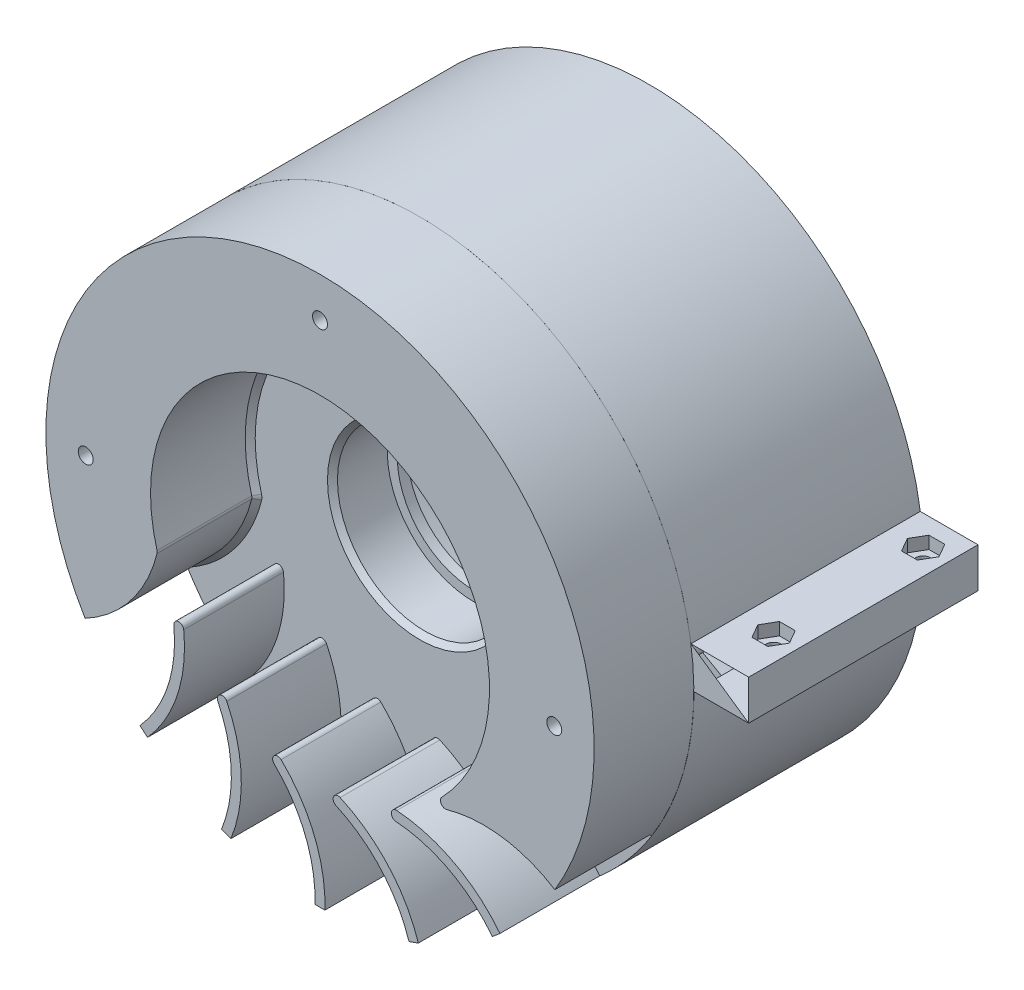
SolidWorks part; units mm, degrees
ref_plane "前视基准面" through (0, 0, 0) normal (0, 0, 1) x (1, 0, 0)
ref_plane "上视基准面" through (0, 0, 0) normal (0, 1, 0) x (1, 0, 0)
ref_plane "右视基准面" through (0, 0, 0) normal (1, 0, 0) x (0, 0, -1)
other "Configuration Table"
sketch "草图1" plane through (0, 0, 0) normal (1, 0, 0) x (0, 0, -1)
  line L0 (0, 0) -> (32.5576, 0) construction
  line L1 (0, 17.5) -> (46, 17.5)
  line L2 (0, 17.5) -> (0, 55)
  line L3 (0, 55) -> (46, 55)
  line L4 (46, 17.5) -> (46, 55)
  dimension "D1" = 17.5
  dimension "D2" = 55
  dimension "D3" = 46
sketch "草图2" plane through (0, 0, 0) normal (0, 0, 1) x (1, 0, 0)
  line L0 (-33.6531, -9.6161) -> (-22.355, -49.1554) construction
  line L3 (-52.8896, -16.3925) -> (-45.4407, -29.2943) construction
  line L4 (-45.7638, -26.4218) -> (-39.6155, -22.872) construction
  line L5 (0, 0) -> (0, -27.9556) construction
  line L6 (-33.6531, -9.6161) -> (-40.2555, -35.993) construction
  circle A0 centre (0, 0) radius 35 construction
  circle A1 centre (0, 0) radius 54 construction
  arc A4 (-33.6531, -9.6161) -> (-46.7654, -27) centre (-60.7125, -2.8429) cw construction
  arc A5 (-46.2654, -27.866) -> (-32.683, -9.859) centre (-60.7125, -2.8429) ccw
  arc A6 (-47.2654, -26.134) -> (-34.6231, -9.3733) centre (-60.7125, -2.8429) ccw
  arc A7 (-47.2654, -26.134) -> (-46.2654, -27.866) centre (-46.7654, -27) ccw construction
  arc A8 (-32.683, -9.859) -> (-34.6231, -9.3733) centre (-33.6531, -9.6161) ccw
  arc A9 (-47.2654, -26.134) -> (-48.1283, -26.6113) centre (-60.7125, -2.8429) cw
  arc A10 (-54.7677, -5.0001) -> (54.7677, -5.0001) centre (0, 0) ccw construction
  arc A11 (-46.2654, -27.866) -> (-47.1283, -28.3448) centre (-60.7125, -2.8429) cw
  arc A12 (-47.1283, -28.3448) -> (-48.1283, -26.6113) centre (0, 0) cw
  point P6 (-38.4429, -19.6404)
  dimension "D1" = 70
  dimension "D2" = 108
  dimension "D3" = 1
  dimension "D4" = 60
  dimension "D5" = 30
extrude "凸台-拉伸1" add sketch "草图2" along normal blind 20 contours A12 A11 A5 A8 A6 A9 region at (-39.1834, -19.2063, 0)
revolve "旋转1" add sketch "草图1" angle 360 about L0
pattern_circular "阵列(圆周)1" count 7 every 20 about axis through (0, 0, 0) along (0, 0, 1) of "凸台-拉伸1"
sketch "草图3" plane through (0, 0, 0) normal (0, 0, 1) x (1, 0, 0)
  arc A9 (-47.1283, -28.3448) -> (47.1103, -28.3747) centre (0, 0) cw
  arc A20 (-32.6916, -9.3414) -> (24.4357, -23.641) centre (0, 0) cw
  arc A22 (24.8796, -23.3748) -> (25.4291, -25.2979) centre (25.1544, -24.3363) ccw construction
  arc A23 (-47.1283, -28.3448) -> (-32.683, -9.859) centre (-60.7125, -2.8429) ccw construction
  arc A24 (-47.1283, -28.3448) -> (-32.683, -9.859) centre (-60.7125, -2.8429) ccw
  arc A25 (47.1103, -28.3747) -> (25.4291, -25.2979) centre (32.8182, -51.1571) ccw
  arc A26 (-32.683, -9.859) -> (-32.6916, -9.3414) centre (-33.6531, -9.6161) ccw
  arc A27 (24.4357, -23.641) -> (25.4291, -25.2979) centre (25.1544, -24.3363) ccw
  arc A28 (47.1103, -28.3747) -> (25.4291, -25.2979) centre (32.8182, -51.1571) ccw construction
extrude "凸台-拉伸2" add sketch "草图3" along normal up to surface (20 mm away) up to face at (-39.6333, -19.0479, 20)
sketch "草图4" plane through (0, 0, -46) normal (0, 0, -1) x (-1, 0, 0)
  line L0 (-50, 0) -> (-47, 0) construction
  line L1 (-45.25, 3.0311) -> (-49.6863, 5.5924)
  line L2 (-45.25, -3.0311) -> (-49.6863, -5.5924)
  line L3 (3.0311, 45.25) -> (5.5924, 49.6863)
  line L4 (-3.0311, 45.25) -> (-5.5924, 49.6863)
  line L5 (0, 50) -> (0, 47) construction
  line L6 (45.25, -3.0311) -> (49.6863, -5.5924)
  line L7 (45.25, 3.0311) -> (49.6863, 5.5924)
  line L8 (50, 0) -> (47, 0) construction
  line L9 (-3.0311, -45.25) -> (-5.5924, -49.6863)
  line L10 (3.0311, -45.25) -> (5.5924, -49.6863)
  line L11 (0, -50) -> (0, -47) construction
  line L12 (-49.9706, -1.7151) -> (-49.9706, 1.7151) construction
  line L13 (-49.9706, 1.7151) -> (-47, 0) construction
  circle A0 centre (0, 0) radius 50 construction
  circle A1 centre (0, 0) radius 55 construction
  arc A2 (-45.25, -3.0311) -> (-45.25, 3.0311) centre (-47, 0) ccw
  circle A3 centre (-47, 0) radius 1.5
  arc A4 (-49.6863, 5.5924) -> (-35.3553, 35.3553) centre (0, 0) cw
  arc A5 (-49.6863, -5.5924) -> (-31.1791, -39.0879) centre (0, 0) ccw
  arc A6 (-3.0311, 45.25) -> (3.0311, 45.25) centre (0, 47) ccw
  circle A7 centre (0, 47) radius 1.5
  arc A8 (5.5924, 49.6863) -> (35.3553, 35.3553) centre (0, 0) cw
  arc A9 (-5.5924, 49.6863) -> (-39.0879, 31.1791) centre (0, 0) ccw
  arc A10 (45.25, 3.0311) -> (45.25, -3.0311) centre (47, 0) ccw
  circle A11 centre (47, 0) radius 1.5
  arc A12 (49.6863, -5.5924) -> (35.3553, -35.3553) centre (0, 0) cw
  arc A13 (49.6863, 5.5924) -> (31.1791, 39.0879) centre (0, 0) ccw
  arc A14 (3.0311, -45.25) -> (-3.0311, -45.25) centre (0, -47) ccw
  circle A15 centre (0, -47) radius 1.5
  arc A16 (-5.5924, -49.6863) -> (-35.3553, -35.3553) centre (0, 0) cw
  arc A17 (5.5924, -49.6863) -> (39.0879, -31.1791) centre (0, 0) ccw
  point P44 (0, 0)
  circle M8 centre (0, 0) radius 17.5
  dimension "D1" = 5
  dimension "D2" = 3
  dimension "D3" = 2
  dimension "D6" = 45
  dimension "D4" = 30
  dimension "D5" = 30
  dimension "D7" = 45
  dimension "D10" = 60
  dimension "D11" = 47
  dimension "D8" = 4
extrude "切除-拉伸1" cut sketch "草图4" against normal offset from surface (35 mm away) 11 contours L10 A17 A12 L6 A10 L7 A13 A8 L3 A6 L4 A9 A4 L1 A2 L2 A5 A16 L9 A14 M8 | A7 | A11 | A15 | A3 region at (46.7655, 5.5288, -46) region at (47, 0, -46) region at (0, 47, -46) region at (-47, 0, -46) region at (0, -47, -46) up to face at (25.6408, -35.7236, 0)
sketch "草图5" plane through (0, 0, -11) normal (0, 0, -1) x (-1, 0, 0)
  circle A0 centre (-47, 0) radius 1.5 construction
  circle A1 centre (0, 47) radius 1.5
  circle A2 centre (0, 47) radius 1.5
  circle A3 centre (-47, 0) radius 1.5
  circle A6 centre (47, 0) radius 1.5 construction
  circle A7 centre (47, 0) radius 1.5
  dimension "D1" = 0
extrude "切除-拉伸2" cut sketch "草图5" against normal up to surface (31 mm away) up to face at (-0.2385, 1.394, 20)
sketch "草图7" plane through (0, 0, -11) normal (0, 0, -1) x (-1, 0, 0)
  circle A10 centre (0, 0) radius 19.5
  circle A11 centre (0, 0) radius 19.5
  circle A12 centre (0, 0) radius 15.5
  circle A13 centre (0, 0) radius 15.5
  dimension "D1" = 2
  dimension "D2" = 2
extrude "凸台-拉伸3" add sketch "草图7" along normal blind 2
chamfer "倒角2" distance 1 angle 45 1 edges at (17.5, 0, 0)
chamfer "倒角3" distance 1 angle 45 4 edges at (-37.9451, -20.6339, 0) (-32.6532, -9.5996, 0) (24.2967, -24.8506, 0) (8.2559, 32.9824, 0)
sketch "草图9" plane through (0, 0, 0) normal (0, 1, 0) x (1, 0, 0)
  line L0 (-55, 46) -> (-55, 0) construction
  line L11 (-55, 46) -> (-55, 0)
  line L12 (-55, 46) -> (-66, 46)
  line L13 (-66, 46) -> (-66, 0)
  line L14 (-66, 0) -> (-55, 0)
  line L15 (0, -36.3) -> (0, 36.3) construction
  line L16 (66, 46) -> (66, 0)
  line L17 (55, 46) -> (66, 46)
  line L18 (55, 46) -> (55, 0)
  line L19 (66, 0) -> (55, 0)
  dimension "D1" = 11
extrude "凸台-拉伸4" add sketch "草图9" along normal blind 8
sketch "草图12" plane through (-55, 0, 0) normal (1, 0, 0) x (0, 0, -1)
  line L4 (0, 0) -> (46, 0)
  line L5 (46, 0) -> (46, 8)
  line L6 (46, 8) -> (0, 8)
  line L7 (0, 8) -> (0, 0)
  line L8 (0, 0) -> (46, 0)
  line L9 (46, 0) -> (46, 8)
  line L10 (46, 8) -> (0, 8)
  line L11 (0, 8) -> (0, 0)
  dimension "D1" = 0
extrude "凸台-拉伸6" add sketch "草图12" along normal up to next
sketch "草图14" plane through (0, 0, 0) normal (0, -1, 0) x (1, 0, 0)
  line L0 (-61, -10) -> (-61, -40) construction
  line L1 (0, -36.3) -> (0, 36.3) construction
  line L4 (-66, -46) -> (-55, -46)
  line L5 (-55, -46) -> (-55, 0)
  line L6 (-55, 0) -> (-66, 0)
  line L7 (-66, 0) -> (-66, -46)
  line L8 (-66, -46) -> (-55, -46) construction
  line L10 (-55, 0) -> (-66, 0) construction
  line L11 (-66, 0) -> (-66, -46) construction
  line L13 (-55, -46) -> (-55, 0)
  circle A0 centre (-61, -10) radius 1.5
  circle A1 centre (-61, -40) radius 1.5
  circle A2 centre (61, -40) radius 1.5
  circle A3 centre (61, -10) radius 1.5
  dimension "D2" = 3
  dimension "D5" = 3
  dimension "D3" = 10
  dimension "D4" = 6
  dimension "D6" = 30
  dimension "D1" = 0
extrude "切除-拉伸3" cut sketch "草图14" against normal up to next contours A1 | A0 | A1 | A3 | A2 region at (-61, 0, -40)
sketch "草图15" plane through (55, 0, 0) normal (-1, 0, 0) x (0, 0, 1)
  line L4 (-46, 0) -> (0, 0)
  line L5 (0, 0) -> (0, 8)
  line L6 (0, 8) -> (-46, 8)
  line L7 (-46, 8) -> (-46, 0)
  line L8 (-46, 0) -> (0, 0)
  line L9 (0, 0) -> (0, 8)
  line L10 (0, 8) -> (-46, 8)
  line L11 (-46, 8) -> (-46, 0)
  dimension "D1" = 0
extrude "凸台-拉伸7" add sketch "草图15" along normal up to next
sketch "草图17" plane through (0, 0, 0) normal (0, -1, 0) x (1, 0, 0)
  line L0 (-61, -10) -> (-61, -40) construction
  line L1 (-57.8246, -40) -> (-59.4123, -37.25)
  line L2 (-59.4123, -37.25) -> (-62.5877, -37.25)
  line L3 (-62.5877, -37.25) -> (-64.1754, -40)
  line L4 (-66, -46) -> (-55, -46)
  line L5 (-55, -46) -> (-55, 0)
  line L6 (-55, 0) -> (-66, 0)
  line L7 (-66, 0) -> (-66, -46)
  line L8 (-66, -46) -> (-55, -46) construction
  line L9 (-55, -46) -> (-55, 0) construction
  line L10 (-55, 0) -> (-66, 0) construction
  line L11 (-66, 0) -> (-66, -46) construction
  line L12 (-64.1754, -40) -> (-62.5877, -42.75)
  line L13 (-62.5877, -42.75) -> (-59.4123, -42.75)
  line L14 (-59.4123, -42.75) -> (-57.8246, -40)
  line L15 (0, -36.3) -> (0, 36.3) construction
  line L16 (-59.4123, -7.25) -> (-62.5877, -7.25)
  line L17 (-62.5877, -7.25) -> (-64.1754, -10)
  line L18 (-64.1754, -10) -> (-62.5877, -12.75)
  line L19 (-62.5877, -12.75) -> (-59.4123, -12.75)
  line L20 (-59.4123, -12.75) -> (-57.8246, -10)
  line L21 (-57.8246, -10) -> (-59.4123, -7.25)
  line L22 (59.4123, -42.75) -> (57.8246, -40)
  line L23 (62.5877, -42.75) -> (59.4123, -42.75)
  line L24 (64.1754, -40) -> (62.5877, -42.75)
  line L25 (62.5877, -37.25) -> (64.1754, -40)
  line L26 (59.4123, -37.25) -> (62.5877, -37.25)
  line L27 (57.8246, -40) -> (59.4123, -37.25)
  line L28 (57.8246, -10) -> (59.4123, -7.25)
  line L29 (59.4123, -12.75) -> (57.8246, -10)
  line L30 (62.5877, -12.75) -> (59.4123, -12.75)
  line L31 (64.1754, -10) -> (62.5877, -12.75)
  line L32 (62.5877, -7.25) -> (64.1754, -10)
  line L33 (59.4123, -7.25) -> (62.5877, -7.25)
  circle A0 centre (-61, -40) radius 1.5 construction
  circle A1 centre (-61, -10) radius 1.5 construction
  circle A2 centre (-61, -40) radius 1.5 construction
  circle A3 centre (-61, -10) radius 1.5 construction
  circle A4 centre (-61, -40) radius 2.75 construction
  circle A5 centre (-61, -10) radius 2.75 construction
  point P19 (-56.8277, -10)
  dimension "D2" = 5.5
  dimension "D3" = 5.5
  dimension "D1" = 0
extrude "切除-拉伸4" cut sketch "草图17" along normal blind 2.5 from surface starting at face at (-61, 8, -41.5)
